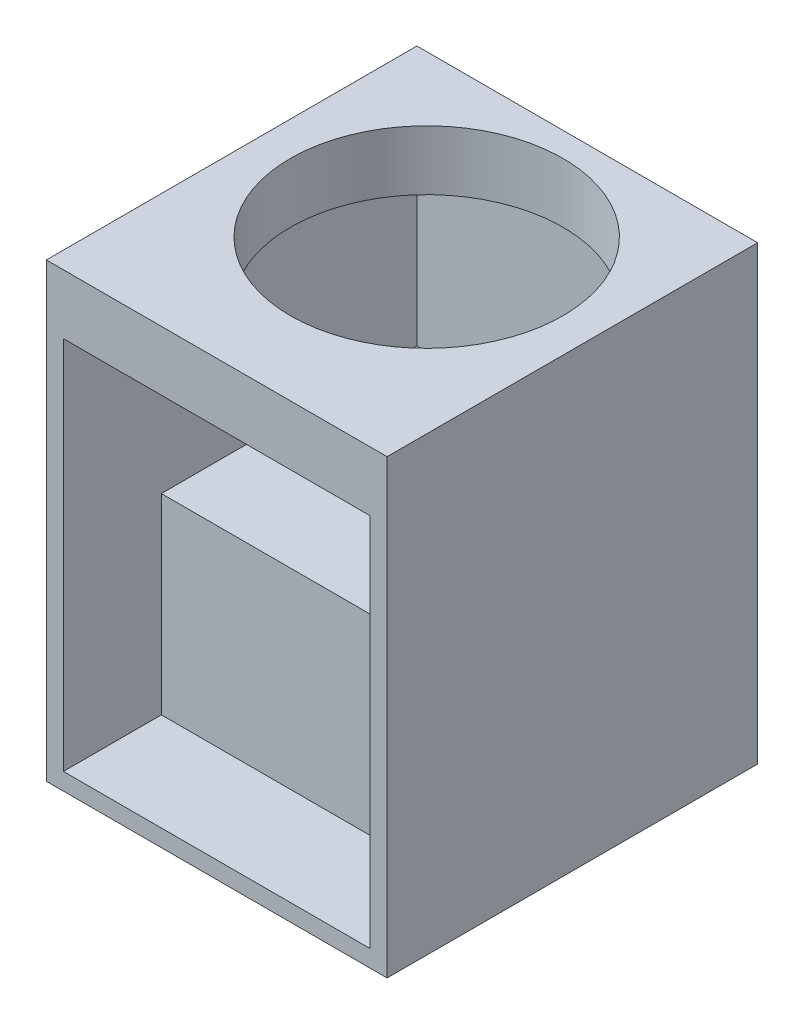
SolidWorks part; units mm, degrees
ref_plane "Front Plane" through (0, 0, 0) normal (0, 0, 1) x (1, 0, 0)
ref_plane "Top Plane" through (0, 0, 0) normal (0, 1, 0) x (1, 0, 0)
ref_plane "Right Plane" through (0, 0, 0) normal (1, 0, 0) x (0, 0, -1)
sketch "Sketch1" plane through (0, 0, 0) normal (0, 1, 0) x (1, 0, 0)
  line L1 (-200, 124) -> (200, 124)
  line L2 (-200, 124) -> (-200, -311)
  line L3 (-200, -311) -> (200, -311)
  line L4 (200, 124) -> (200, -311)
  circle A0 centre (0, -64.5) radius 160 construction
  point P4 (0, 124)
  dimension "D5" = 320
  dimension "D1" = 124
  dimension "D2" = 435
  dimension "D3" = 400
  dimension "D4" = 64.5
extrude "Boss-Extrude1" add sketch "Sketch1" along normal blind 480
sketch "Sketch4" plane through (0, 0, -124) normal (0, 0, -1) x (-1, 0, 0)
  line L1 (-175, 225) -> (175, 225)
  line L2 (-175, 225) -> (-175, 25)
  line L3 (-175, 25) -> (175, 25)
  line L4 (175, 225) -> (175, 25)
  line L5 (200, 0) -> (-200, 0) construction
  line L6 (-200, 480) -> (-200, 0) construction
  point P4 (0, 25)
  dimension "D1" = 25
  dimension "D2" = 25
  dimension "D3" = 200
extrude "Cut-Extrude1" cut sketch "Sketch4" against normal blind 300
shell "Shell1" thickness 20 removed face at (0, 240, 311)
sketch "Sketch5" plane through (0, 480, 0) normal (0, 1, 0) x (1, 0, 0)
  line L4 (-200, 124) -> (-200, -311)
  line L5 (-200, -311) -> (200, -311)
  line L6 (200, -311) -> (200, 124)
  line L7 (200, 124) -> (-200, 124)
  line L8 (-200, 124) -> (-200, -311)
  line L9 (-200, -311) -> (200, -311)
  line L10 (200, -311) -> (200, 124)
  line L11 (200, 124) -> (-200, 124)
  dimension "D1" = 0
extrude "Boss-Extrude2" add sketch "Sketch5" along normal blind 50 contours L8 L9 L10 L11
sketch "Sketch3" plane through (0, 530, 0) normal (0, 1, 0) x (1, 0, 0)
  circle A0 centre (0, -64.5) radius 160 construction
  circle A2 centre (0, -64.5) radius 160
extrude "Cut-Extrude2" cut sketch "Sketch3" against normal up to surface (70 mm away) up to face at (0, 460, 103.5)
sketch "Sketch6" plane through (0, 245, 0) normal (0, 1, 0) x (1, 0, 0)
  circle A0 centre (0, 20) radius 42.5
  dimension "D1" = 85
  dimension "D2" = 84.5
extrude "Cut-Extrude3" cut sketch "Sketch6" against normal up to surface (20 mm away) up to face at (0, 225, 26)
